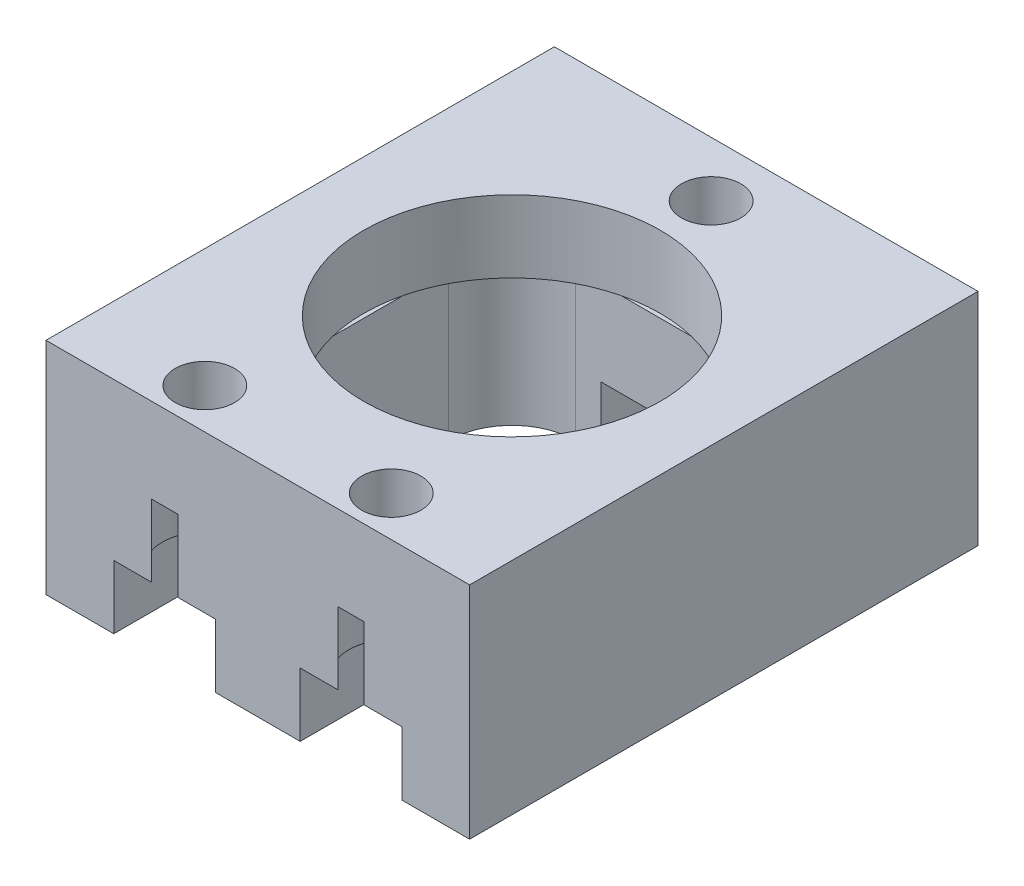
SolidWorks part; units mm, degrees
ref_plane "前视基准面" through (0, 0, 0) normal (0, 0, 1) x (1, 0, 0)
ref_plane "上视基准面" through (0, 0, 0) normal (0, 1, 0) x (1, 0, 0)
ref_plane "右视基准面" through (0, 0, 0) normal (1, 0, 0) x (0, 0, -1)
other "Configuration Table"
sketch "草图1" plane through (0, 0, 0) normal (0, 1, 0) x (1, 0, 0)
  line L7 (-5, -6) -> (5, -6)
  line L8 (-5, -6) -> (-5, 6)
  line L9 (-5, 6) -> (5, 6)
  line L10 (5, -6) -> (5, 6)
  circle A0 centre (0, 0) radius 3.5
  point P0 (0, 0)
  point P5 (0, 0)
  dimension "D1" = 7
  dimension "D2" = 10
  dimension "D3" = 6
  dimension "D4" = 6
  dimension "D5" = 5
extrude "凸台-拉伸1" add sketch "草图1" along normal blind 1.7 contours L9 L10 L7 L8 | A0
sketch "草图4" plane through (0, 0, 0) normal (0, -1, 0) x (1, 0, 0)
  line L0 (-5, 6) -> (5, 6) construction
  line L1 (3.4, -3.4) -> (-3.4, -3.4)
  line L2 (3.4, -3.4) -> (3.4, 4.1)
  line L3 (3.4, 4.1) -> (-3.4, 4.1)
  line L4 (-3.4, -3.4) -> (-3.4, 4.1)
  line L5 (-5, 6) -> (5, 6)
  line L6 (-5, 6) -> (-5, -6)
  line L7 (-5, -6) -> (5, -6)
  line L8 (5, 6) -> (5, -6)
  line L9 (-5, -6) -> (5, -6) construction
  line L11 (-3.4, 4.1) -> (-1, 4.1)
  line L12 (-3.4, 4.1) -> (-3.4, 6)
  line L13 (-3.4, 6) -> (-1, 6)
  line L14 (-1, 4.1) -> (-1, 6)
  line L15 (3.4, 4.1) -> (1, 4.1)
  line L16 (3.4, 4.1) -> (3.4, 6)
  line L17 (3.4, 6) -> (1, 6)
  line L18 (1, 4.1) -> (1, 6)
  line L19 (-1.3, -3.4) -> (1.3, -3.4)
  line L20 (-1.3, -3.4) -> (-1.3, -6)
  line L21 (-1.3, -6) -> (1.3, -6)
  line L22 (1.3, -3.4) -> (1.3, -6)
  circle A0 centre (-1.9, -1.9) radius 1.5
  circle A1 centre (1.9, -1.9) radius 1.5
  circle M9 centre (0, 0) radius 3.5
  dimension "D5" = 3
  dimension "D1" = 3.4
  dimension "D2" = 4.1
  dimension "D3" = 3.4
  dimension "D4" = 3.4
  dimension "D6" = 5
  dimension "D7" = 5
  dimension "D8" = 1
  dimension "D9" = 1
  dimension "D10" = 1.3
  dimension "D11" = 1.3
extrude "凸台-拉伸2" add sketch "草图4" along normal blind 3.5 contours A0 M9 | A0 M9 | A1 M9 | A1 M9 | A1 L2 L4 A0 L1 M9 | L4 L2 L3 M9 | A0 L4 M9 | A1 L2 M9 | A1 L1 M9 | A0 L1 M9 | L8 L7 L6 L5 region at (1.279, 0, -3.3571) region at (2.6319, 0, -2.6319) region at (3.3571, 0, -1.279) region at (0, 0, 0.7277) region at (1.7105, 0, -1.7105) region at (0, 0, 3.5755) region at (-1.279, 0, -3.3571) region at (-1.7105, 0, -1.7105) region at (-2.6319, 0, -2.6319) region at (-3.3571, 0, -1.279)
extrude "切除-拉伸2" cut sketch "草图4<3>" against normal blind 1.5 from surface contours L3 L14 L5 L12 | L18 L3 L16 L5 | L22 L1 L20 L7 M9 | L1 M9 region at (0, 0, -4.721) region at (0, 0, -3.44) region at (2.2, 0, 5.05) region at (-2.2, 0, 5.05) starting at face at (0, -3.5, -0.5036)
sketch "草图4<3>" plane through (0, 0, 0) normal (0, -1, 0) x (1, 0, 0) same geometry as "草图4"
sketch "草图5" plane through (0, 1.7, 0) normal (0, 1, 0) x (1, 0, 0)
  line L0 (0, 6) -> (0, 3.4) construction
  line L1 (-1.3, 6) -> (1.3, 6) construction
  line L2 (1.3, 3.4) -> (-1.3, 3.4) construction
  line L3 (2.2, -4.1) -> (2.2, -6) construction
  line L4 (3.4, -4.1) -> (1, -4.1) construction
  line L5 (3.4, -6) -> (1, -6) construction
  line L6 (-2.2, -4.1) -> (-2.2, -6) construction
  line L7 (-1, -4.1) -> (-3.4, -4.1) construction
  line L8 (-1, -6) -> (-3.4, -6) construction
  line L9 (0, -4.1) -> (0, -6) construction
  line L10 (1, -4.1) -> (-1, -4.1) construction
  line L11 (-1, -6) -> (1, -6) construction
  line L12 (-5, 6) -> (-1.3, 6) construction
  line L13 (-5, -6) -> (-5, 6) construction
  line L14 (5, -6) -> (5, 6) construction
  circle A0 centre (0, 4.7) radius 0.7
  circle A1 centre (2.2, -5.05) radius 1
  circle A2 centre (2.2, -5.05) radius 0.7
  circle A3 centre (-2.2, -5.05) radius 1
  circle A4 centre (-2.2, -5.05) radius 0.7
  circle A5 centre (0, 4.7) radius 1
  circle A6 centre (3.5, 4.5) radius 0.3
  circle A7 centre (-3.5, 4.5) radius 0.3
  circle A8 centre (0, -5.05) radius 0.3
  point P43 (2.8966, 4.5)
  dimension "D1" = 2
  dimension "D2" = 1.4
  dimension "D3" = 0.6
  dimension "D4" = 1.5
  dimension "D5" = 1.5
  dimension "D6" = 1.5
extrude "切除-拉伸3" cut sketch "草图5" against normal through all contours A2 | A4 | A0
extrude "切除-拉伸4" cut sketch "草图5<3>" along normal offset from surface (1.7 mm away) 2 from surface contours A1 | A5 | A3 up to face at (2.2, 1.7, 5.75) starting at face at (0, -2, -4)
sketch "草图5<3>" plane through (0, 1.7, 0) normal (0, 1, 0) x (1, 0, 0) same geometry as "草图5"
extrude "切除-拉伸5" cut sketch "草图5<4>" along normal blind 4 from surface contours A6 | A7 | A8 starting at face at (-3.0872, -3.5, -1.2872)
sketch "草图5<4>" plane through (0, 1.7, 0) normal (0, 1, 0) x (1, 0, 0) same geometry as "草图5"
